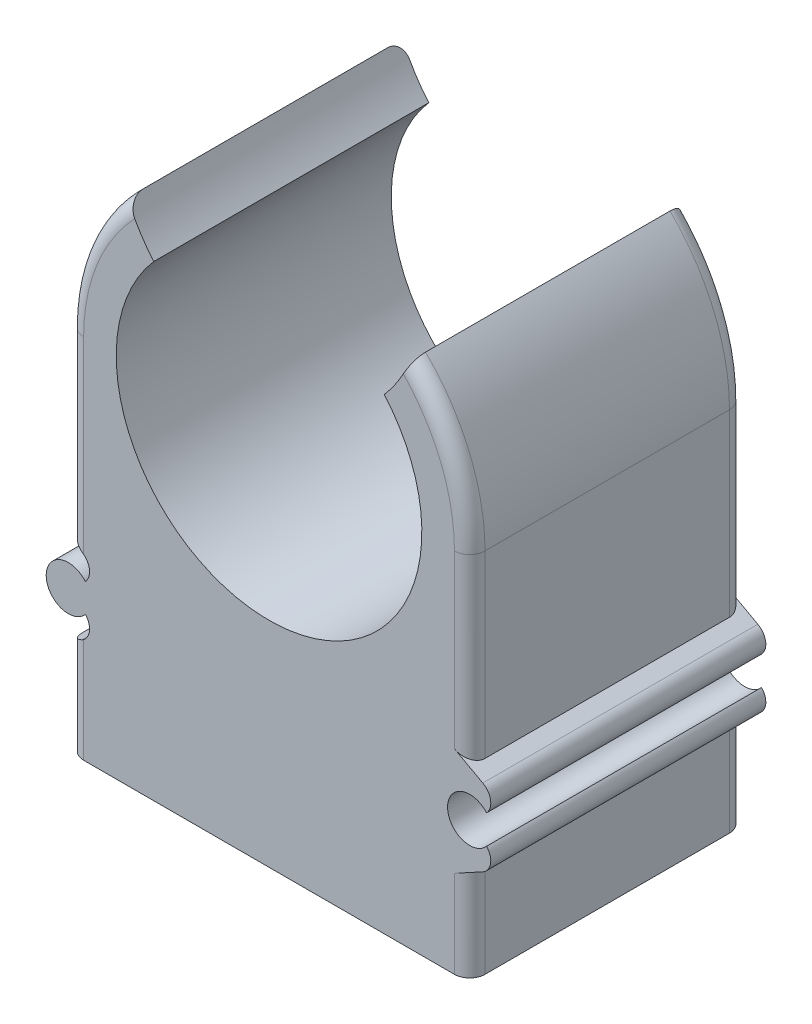
SolidWorks part; units mm, degrees
ref_plane "Front Plane" through (0, 0, 0) normal (0, 0, 1) x (1, 0, 0)
ref_plane "Top Plane" through (0, 0, 0) normal (0, 1, 0) x (1, 0, 0)
ref_plane "Right Plane" through (0, 0, 0) normal (1, 0, 0) x (0, 0, -1)
sketch "Sketch1" plane through (0, 0, 0) normal (0, 0, 1) x (1, 0, 0)
  line L0 (-10.4247, -14.0706) -> (-10.4247, -19.05)
  line L2 (10.4247, -14.0706) -> (10.4247, -19.05)
  line L3 (-10.4247, -19.05) -> (10.4247, -19.05)
  line L6 (-10.4247, 0) -> (-10.4247, -9.3355)
  line L7 (10.4247, 0) -> (10.4247, -9.3355)
  line L8 (-9.5421, -10.9633) -> (-8.1932, -10.5806)
  line L9 (-8.1932, -10.5806) -> (-10.4247, -9.3355)
  line L10 (-9.5421, -12.4428) -> (-8.1932, -12.8255)
  line L11 (-8.1932, -12.8255) -> (-10.4247, -14.0706)
  line L12 (12.6563, -12.8547) -> (10.4247, -14.0706)
  line L13 (12.6563, -10.5514) -> (10.4247, -9.3355)
  line L14 (11.2975, -10.9517) -> (12.6563, -10.5514)
  line L15 (11.2975, -12.4544) -> (12.6563, -12.8547)
  arc A1 (10.4247, 0) -> (-10.4247, 0) centre (0, 0) ccw
  arc A2 (-9.5421, -10.9633) -> (-9.5421, -12.4428) centre (-10.4247, -11.7031) ccw
  arc A3 (11.2975, -10.9517) -> (11.2975, -12.4544) centre (10.4247, -11.7031) ccw
  circle A4 centre (0, 0) radius 7.9375
  dimension "D1" = 19.05
  dimension "D2" = 15.875
  dimension "D3" = 20.8495
  dimension "D4" = 2.3033
  dimension "D5" = 4.7352
  dimension "D6" = 2.2316
  dimension "D7" = 315
  dimension "D8" = 315
  dimension "D9" = 315
  dimension "D10" = 315
  dimension "D11" = 2.5555
  dimension "D12" = 2.3676
  dimension "D13" = 2.3033
  dimension "D14" = 2.2316
  dimension "D15" = 4.7352
  dimension "D16" = 7.3469
  dimension "D17" = 4.9794
extrude "Boss-Extrude19" add sketch "Sketch1" along normal mid plane 14.2875
sketch "Sketch2" plane through (0, 0, 7.1437) normal (0, 0, 1) x (1, 0, 0)
  circle A0 centre (0, 10.4247) radius 7.9375
  arc A1 (10.4247, 0) -> (-10.4247, 0) centre (0, 0) ccw construction
extrude "Cut-Extrude2" cut sketch "Sketch2" against normal through all
fillet "Fillet6" radius 0.7937 4 edges at (-8.1932, -12.8255, 0) (-8.1932, -10.5806, 0) (12.6563, -12.8547, 0) (12.6563, -10.5514, 0)
fillet "Fillet7" radius 0.7937 12 edges at (-10.4247, -16.5603, -7.1437) (-10.4247, -4.6677, -7.1437) (-9.6226, 4.01, -7.1437) (9.6226, 4.01, -7.1437) (10.4247, -4.6677, -7.1437) (10.4247, -16.5603, -7.1437) (10.4247, -16.5603, 7.1437) (-10.4247, -16.5603, 7.1437) (-10.4247, -4.6677, 7.1437) (-9.6226, 4.01, 7.1437) (9.6226, 4.01, 7.1437) (10.4247, -4.6677, 7.1437)
